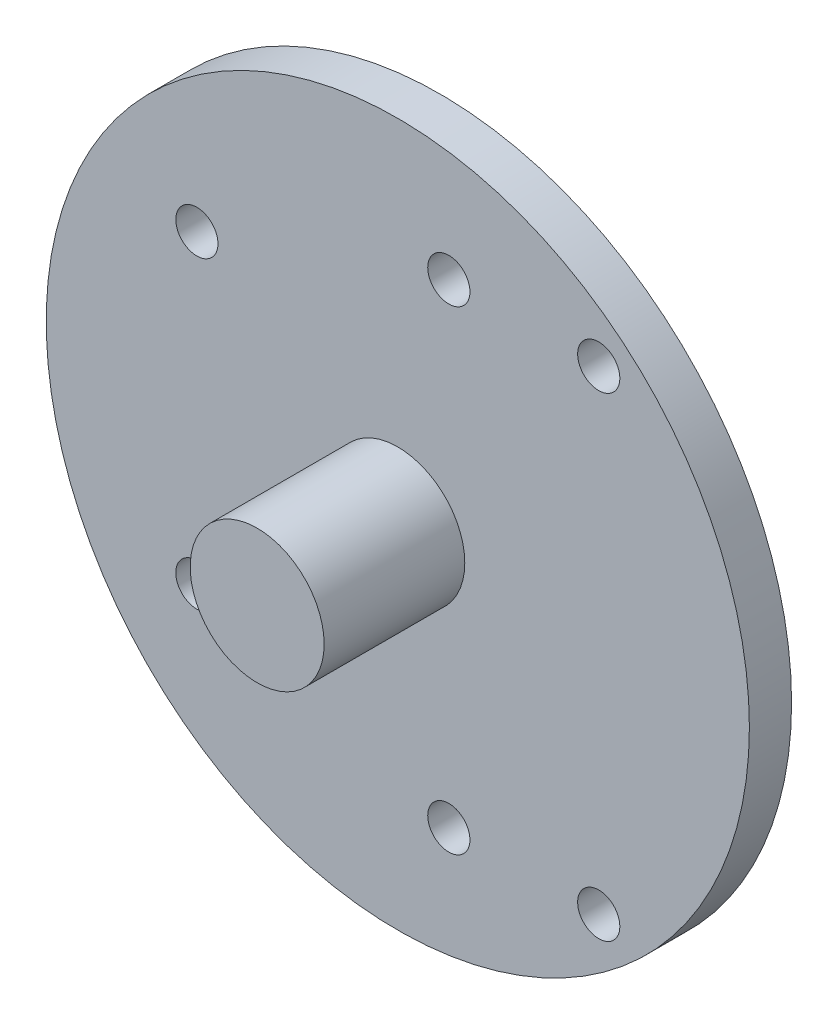
SolidWorks part; units mm, degrees
ref_plane "Front" through (0, 0, 0) normal (0, 0, 1) x (1, 0, 0)
ref_plane "Top" through (0, 0, 0) normal (0, 1, 0) x (1, 0, 0)
ref_plane "Right" through (0, 0, 0) normal (1, 0, 0) x (0, 0, -1)
sketch "Sketch1" plane through (0, 0, 0) normal (0, 0, 1) x (1, 0, 0)
  circle A0 centre (0, 0) radius 25
extrude "Extrude1" add sketch "Sketch1" along normal blind 3
sketch "Sketch2" plane through (0, 0, 3) normal (0, 0, 1) x (1, 0, 0)
  circle A0 centre (0, 0) radius 4.7625
extrude "Extrude2" add sketch "Sketch2" along normal blind 10
sketch "Sketch3" plane through (0, 0, 0) normal (0, 0, -1) x (-1, 0, 0)
  circle A0 centre (-14.2875, 16.875) radius 1.5
  circle A1 centre (14.2875, 10.875) radius 1.5
  circle A2 centre (14.2875, -10.875) radius 1.5
  circle A3 centre (-14.2875, -16.875) radius 1.5
  circle A4 centre (-3.6275, 16.875) radius 1.5
  circle A5 centre (-3.6275, -16.875) radius 1.5
extrude "Cut-Extrude1" cut sketch "Sketch3" against normal through all
